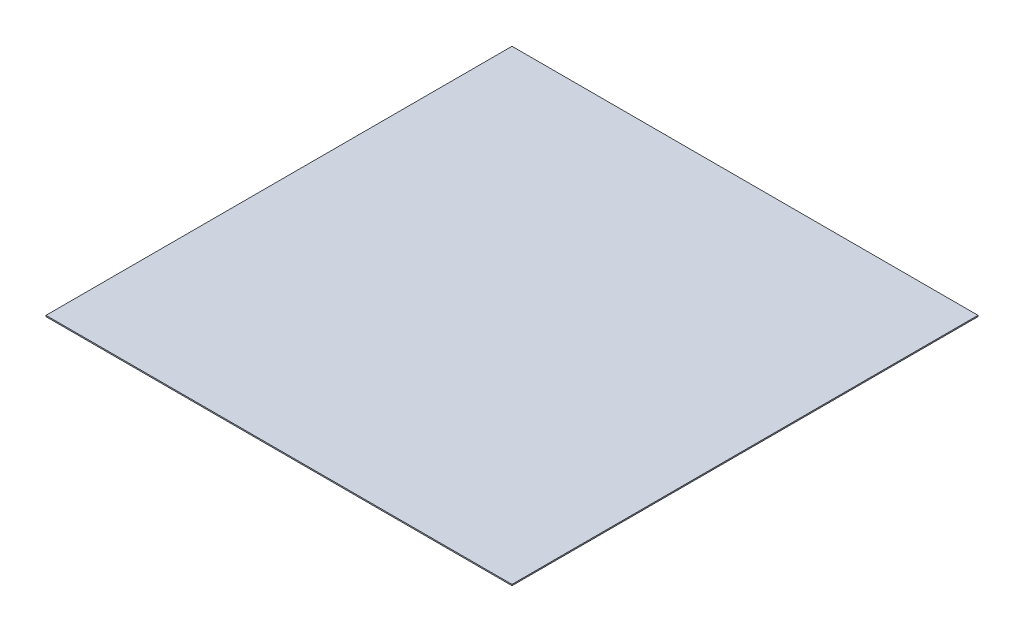
SolidWorks part; units mm, degrees
material "Pine"
ref_plane "Front" through (0, 0, 0) normal (0, 0, 1) x (1, 0, 0)
ref_plane "Top" through (0, 0, 0) normal (0, 1, 0) x (1, 0, 0)
ref_plane "Right" through (0, 0, 0) normal (1, 0, 0) x (0, 0, -1)
sketch "Sketch1" plane through (0, 0, 0) normal (0, 1, 0) x (1, 0, 0)
  line L1 (-2463.8, 2463.8) -> (2463.8, 2463.8)
  line L2 (-2463.8, 2463.8) -> (-2463.8, -2463.8)
  line L3 (-2463.8, -2463.8) -> (2463.8, -2463.8)
  line L4 (2463.8, 2463.8) -> (2463.8, -2463.8)
  line L5 (-2463.8, 2463.8) -> (2463.8, -2463.8) construction
  line L6 (-2463.8, -2463.8) -> (2463.8, 2463.8) construction
  point P0 (0, 0)
  dimension "D1" = 4927.6
  dimension "D2" = 4927.6
extrude "Boss-Extrude1" add sketch "Sketch1" along normal blind 12.7
